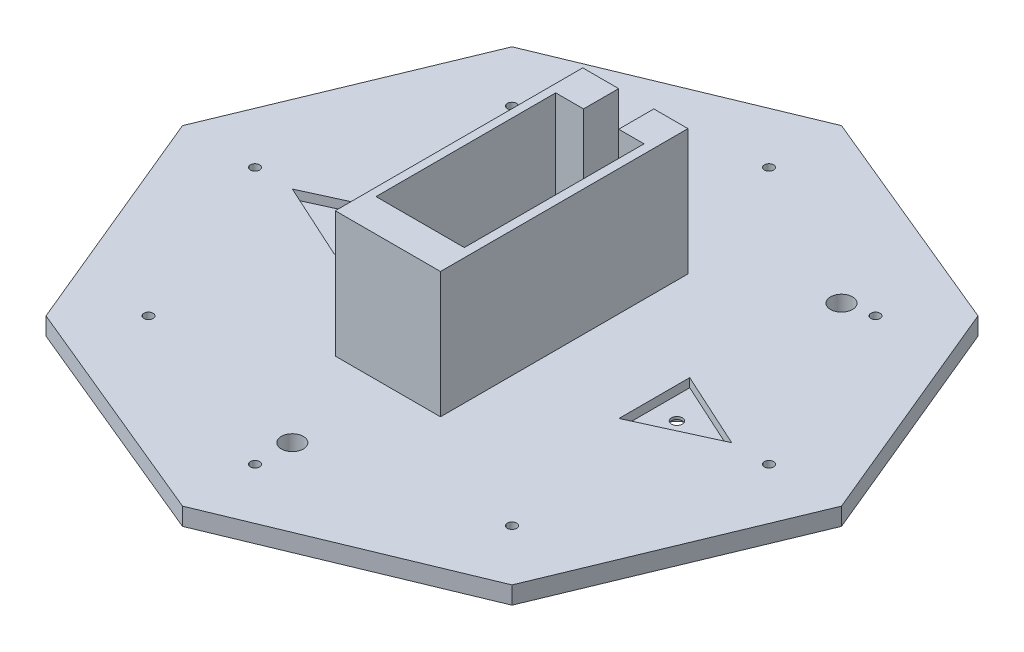
SolidWorks part; units mm, degrees
ref_plane "Ebene vorne" through (0, 0, 0) normal (0, 0, 1) x (1, 0, 0)
ref_plane "Ebene oben" through (0, 0, 0) normal (0, 1, 0) x (1, 0, 0)
ref_plane "Ebene rechts" through (0, 0, 0) normal (1, 0, 0) x (0, 0, -1)
sketch "Skizze2" plane through (0, 0, 0) normal (0, 1, 0) x (1, 0, 0)
  line L0 (-75, 0) -> (75, 0) construction
  line L1 (-55, 0) -> (55, 0) construction
  line L2 (0, -55) -> (0, 55) construction
  line L3 (-53.033, -53.033) -> (53.033, 53.033)
  line L4 (53.033, -53.033) -> (-53.033, 53.033)
  line L5 (-75, 0) -> (-53.033, 53.033)
  line L6 (-53.033, 53.033) -> (0, 75)
  line L7 (0, 75) -> (53.033, 53.033)
  line L8 (75, 0) -> (53.033, 53.033)
  line L9 (75, 0) -> (53.033, -53.033)
  line L10 (53.033, -53.033) -> (0, -75)
  line L11 (0, -75) -> (-53.033, -53.033)
  line L12 (-75, 0) -> (-53.033, -53.033)
  point P10 (0, 0)
  point P13 (0, 0)
  dimension "D1" = 150
  dimension "D2" = 75
  dimension "D3" = 150
  dimension "D4" = 150
  dimension "D5" = 45
  dimension "D6" = 45
  dimension "D7" = 75
  dimension "D8" = 75
extrude "Aufsatz-Linear austragen1" add sketch "Skizze2" along normal blind 3 and the other way blind 1 contours L7 L6 L4 L3 | L3 L0 L8 | L0 L4 L9 | L11 L10 L4 L3 | L5 L0 L4 | L0 L12 L3 region at (-42.6777, 0, -17.6777) region at (-42.6777, 0, 17.6777) region at (42.6777, 0, -17.6777) region at (0, 0, 42.6777) region at (0, 0, -42.6777) region at (42.6777, 0, 17.6777)
sketch "Skizze5" plane through (0, 0, 0) normal (0, 1, 0) x (1, 0, 0)
  line L17 (-4, 28.2826) -> (-4, 20.2826)
  line L18 (-12.1859, -28.0429) -> (11.7641, -28.0429)
  line L19 (-12.1859, -28.0429) -> (-12.1859, 28.2826)
  line L20 (-12.1859, 28.2826) -> (-4, 28.2826)
  line L21 (11.7641, -28.0429) -> (11.7641, 28.2826)
  line L24 (-10.3359, -20.6174) -> (9.7641, -20.6174)
  line L25 (-10.3359, -20.6174) -> (-10.3359, 20.2826)
  line L26 (-10.3359, 20.2826) -> (-4, 20.2826)
  line L27 (9.7641, -20.6174) -> (9.7641, 20.2826)
  line L31 (4, 20.2826) -> (4, 28.2826)
  line L32 (0, -17.9575) -> (0, 17.9575) construction
  line L33 (4, 28.2826) -> (11.7641, 28.2826)
  line L34 (4, 20.2826) -> (9.7641, 20.2826)
  dimension "D7" = 20.1
  dimension "D8" = 40.9
  dimension "D9" = 2
  dimension "D10" = 8
  dimension "D11" = 4
  dimension "D12" = 4
extrude "Aufsatz-Linear austragen3" add sketch "Skizze5" along normal blind 31.65
sketch "Skizze7" plane through (0, 3, 0) normal (0, 1, 0) x (1, 0, 0)
  line L0 (-17.9575, 0) -> (17.9575, 0) construction
  line L5 (-35, -40) -> (33.3537, 38.1186) construction
  line L6 (-33.3537, 38.1186) -> (35, -40) construction
  circle A0 centre (35, 40) radius 2.5
  circle A1 centre (-35, 40) radius 2.5
  circle A2 centre (0, -50) radius 2.5
  point P0 (0, 0)
  dimension "D3" = 5
  dimension "D4" = 5
  dimension "D5" = 5
  dimension "D6" = 50
  dimension "D1" = 80
  dimension "D2" = 70
extrude "Schnitt-Linear austragen2" cut sketch "Skizze7" against normal through all
sketch "Skizze8" plane through (0, 3, 0) normal (0, 1, 0) x (1, 0, 0)
  line L0 (-75, 0) -> (75, 0) construction
  line L7 (-32.4, 8.05) -> (-32.4, -8.05)
  line L8 (-44.0888, 2.7037) -> (-32.4, -8.05) construction
  line L9 (-44.0888, -2.7037) -> (-32.4, 8.05) construction
  line L12 (32.4, 8.05) -> (32.4, -8.05)
  line L15 (32.4, 8.05) -> (44.053, -2.6707) construction
  line L16 (32.4, -8.05) -> (44.0888, 2.7037) construction
  line L18 (0, -17.9575) -> (0, 17.9575) construction
  line L19 (-50, 0) -> (-32.4, -8.05)
  line L21 (-32.4, 8.05) -> (-50, 0)
  line L22 (32.4, -8.05) -> (50, 0)
  line L23 (50, 0) -> (32.4, 8.05)
  line L24 (32.4, -8.05) -> (32.4, 8.05)
  point P2 (-41.15, 0)
  point P7 (41.15, 0)
  dimension "D1" = 32.4
  dimension "D2" = 32.4
  dimension "D3" = 16.1
  dimension "D4" = 50
  dimension "D5" = 50
  dimension "D6" = 16.1
extrude "Schnitt-Linear austragen6" cut sketch "Skizze8" against normal blind 2 contours L7 L21 L19 | L22 L23 L12 region at (-38.2667, 3, 0) region at (38.2667, 3, 0)
sketch "Skizze10" plane through (0, 1, 0) normal (0, 1, 0) x (1, 0, 0)
  line L1 (-0.013, 21.1078) -> (0.0217, -30.9037) construction
  line L7 (41.9977, 0.05) -> (22.7023, 0.05) construction
  circle A0 centre (-37.4878, 0) radius 1.25
  circle A1 centre (37.49, 0.05) radius 1.25
  dimension "D1" = 2.5
  dimension "D2" = 0
  dimension "D3" = 37.4889
extrude "Schnitt-Linear austragen7" cut sketch "Skizze10" against normal through all
sketch "Skizze11" plane through (0, -1, 0) normal (0, -1, 0) x (1, 0, 0)
  circle A0 centre (-37.4878, 0) radius 2.75
  circle A1 centre (37.49, -0.05) radius 2.75
  dimension "D1" = 5.5
  dimension "D2" = 5.5
extrude "Schnitt-Linear austragen8" cut sketch "Skizze11" against normal blind 1.4
sketch "Skizze14" plane through (0, 3, 0) normal (0, 1, 0) x (1, 0, 0)
  line L0 (0, 0) -> (-51.0988, 51.0988) construction
  line L1 (-51.0988, 51.0988) -> (0, 0) construction
  line L2 (0, 0) -> (44.6211, 44.6211) construction
  line L3 (44.6211, 44.6211) -> (0, 0) construction
  line L4 (0, 0) -> (42.9287, -42.9287) construction
  line L5 (42.9287, -42.9287) -> (0, 0) construction
  line L6 (0, 0) -> (-43.4336, -43.4336) construction
  circle A1 centre (-58.5, 0) radius 1.05
  circle A2 centre (0, 58.5) radius 1.05
  circle A3 centre (-41.3657, 41.3657) radius 1.05
  circle A4 centre (41.3657, 41.3657) radius 1.05
  circle A5 centre (58.5, 0) radius 1.05
  circle A6 centre (41.3657, -41.3657) radius 1.05
  circle A7 centre (-41.3657, -41.3657) radius 1.05
  circle A8 centre (0, -58.5) radius 1.05
  dimension "D2" = 2.1
  dimension "D3" = 2.1
  dimension "D4" = 2.1
  dimension "D5" = 2.1
  dimension "D6" = 2.1
  dimension "D7" = 2.1
  dimension "D8" = 2.1
extrude "Schnitt-Linear austragen9" cut sketch "Skizze14" against normal blind 10
